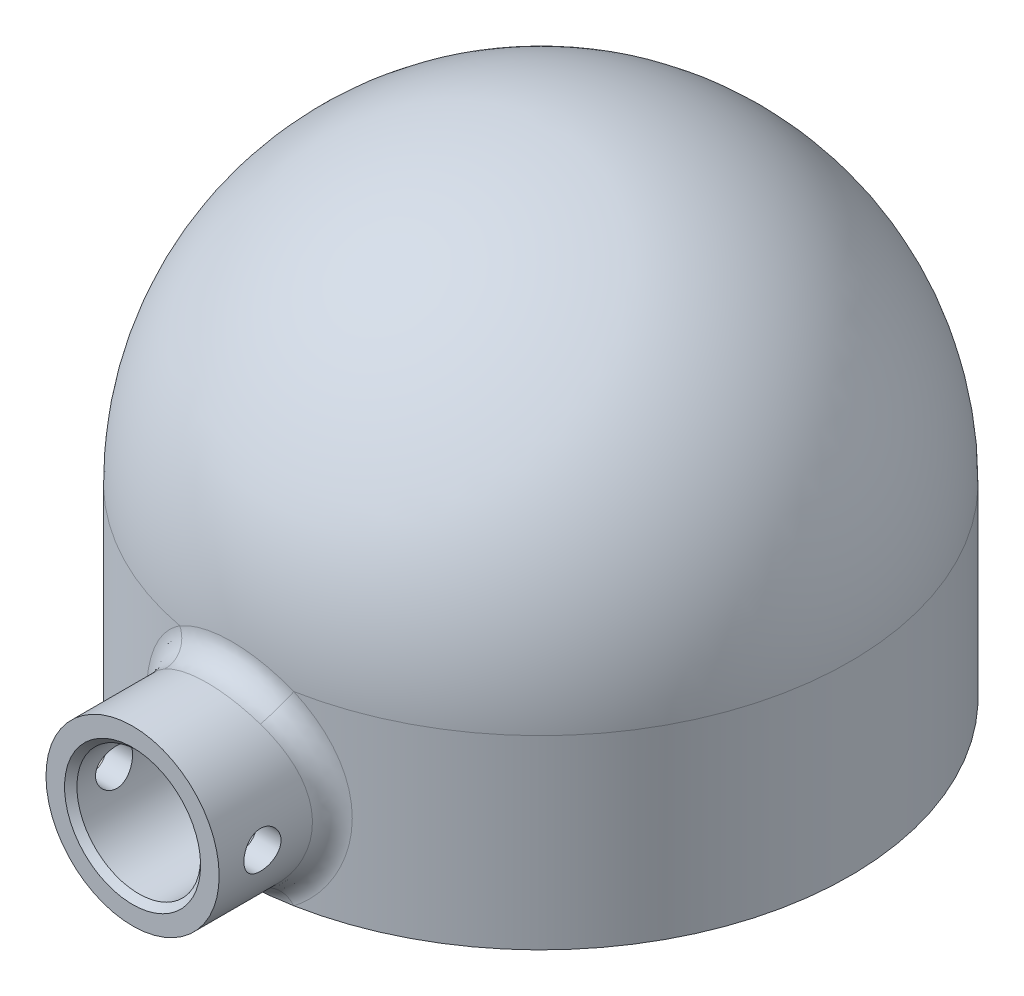
SolidWorks part; units mm, degrees
ref_plane "Ön Düzlem" through (0, 0, 0) normal (0, 0, 1) x (1, 0, 0)
ref_plane "Üst Düzlem" through (0, 0, 0) normal (0, 1, 0) x (1, 0, 0)
ref_plane "Sağ Düzlem" through (0, 0, 0) normal (1, 0, 0) x (0, 0, -1)
sketch "Sketch4" plane through (0, 0, 0) normal (0, 0, 1) x (1, 0, 0)
  line L0 (0, 0) -> (0, 40) construction
  line L1 (-25, 15) -> (-25, 0)
  line L2 (-22, 15) -> (-22, 0)
  line L3 (0, 37) -> (0, 40)
  line L4 (-25, 0) -> (-22, 0)
  arc A0 (0, 40) -> (-25, 15) centre (0, 15) ccw
  arc A1 (0, 37) -> (-22, 15) centre (0, 15) ccw
  dimension "D1" = 25
  dimension "D2" = 15
  dimension "D3" = 3
revolve "Revolve2" add sketch "Sketch4" angle 360 about L0
ref_plane "Plane1" through (0, 0, 25) normal (0, 0, 1) x (1, 0, 0)
sketch "Sketch9" plane through (0, 0, 25) normal (0, 0, 1) x (1, 0, 0)
  line L0 (-25, 0) -> (25, 0) construction
  circle A0 centre (0, 7.5) radius 7
  circle A1 centre (0, 7.5) radius 5
  dimension "D1" = 14
  dimension "D2" = 7.5
  dimension "D3" = 2
extrude "Boss-Extrude2" add sketch "Sketch9" along normal blind 8 and the other way up to surface other way up to face at (0, 0, -25)
sketch "Sketch10" plane through (0, 0, 25) normal (0, 0, 1) x (1, 0, 0)
  circle A0 centre (0, 7.5) radius 5 construction
  circle A1 centre (0, 7.5) radius 5
extrude "Cut-Extrude3" cut sketch "Sketch10" against normal blind 8
fillet "Fillet2" radius 2 1 edges at (6.8758, 8.8128, 24.0359)
chamfer "Chamfer1" distance 0.5 angle 45 1 edges at (5, 7.5, 33)
sketch "Sketch12" plane through (0, 0, 0) normal (1, 0, 0) x (0, 0, -1)
  line L0 (-33, 14.5) -> (-33, 0.5) construction
  line L1 (-33, 7.5) -> (-31.5808, 7.5) construction
  circle A0 centre (-29.5, 7.5) radius 1.5
  dimension "D1" = 3
  dimension "D2" = 3.5
extrude "Cut-Extrude5" cut sketch "Sketch12" against normal blind 10 and the other way blind 10
